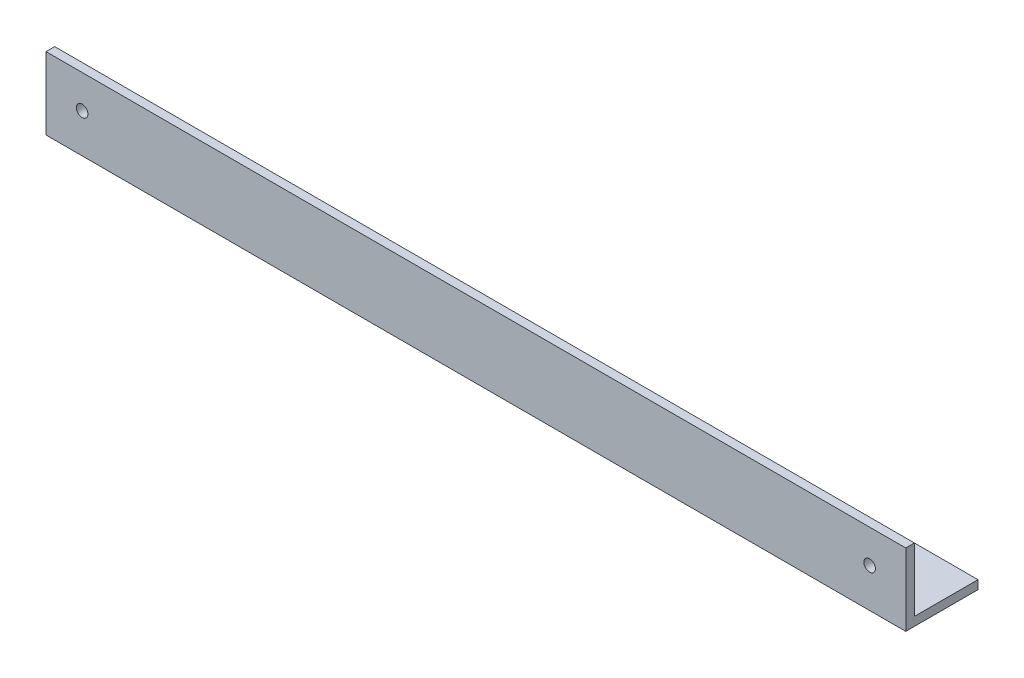
SolidWorks part; units mm, degrees
ref_plane "Спереди" through (0, 0, 0) normal (0, 0, 1) x (1, 0, 0)
ref_plane "Сверху" through (0, 0, 0) normal (0, 1, 0) x (1, 0, 0)
ref_plane "Справа" through (0, 0, 0) normal (1, 0, 0) x (0, 0, -1)
sketch "Эскиз1" plane through (0, 0, 0) normal (1, 0, 0) x (0, 0, -1)
  line L0 (0, 0) -> (50, 0)
  line L5 (0, 50) -> (0, 0)
extrude "Вытянуть-Тонкостенный2" add sketch "Эскиз1" along normal blind 595 thin thin type one direction reverse wall 6
sketch "Эскиз2" plane through (0, 0, 0) normal (0, 0, 1) x (1, 0, 0)
  line L0 (297.5, 50) -> (297.5, -14.5618) construction
  line L1 (595, 50) -> (0, 50) construction
  circle A0 centre (25, 27) radius 4
  circle A1 centre (570, 27) radius 4
extrude "Вырез-Вытянуть1" cut sketch "Эскиз2" against normal through all
